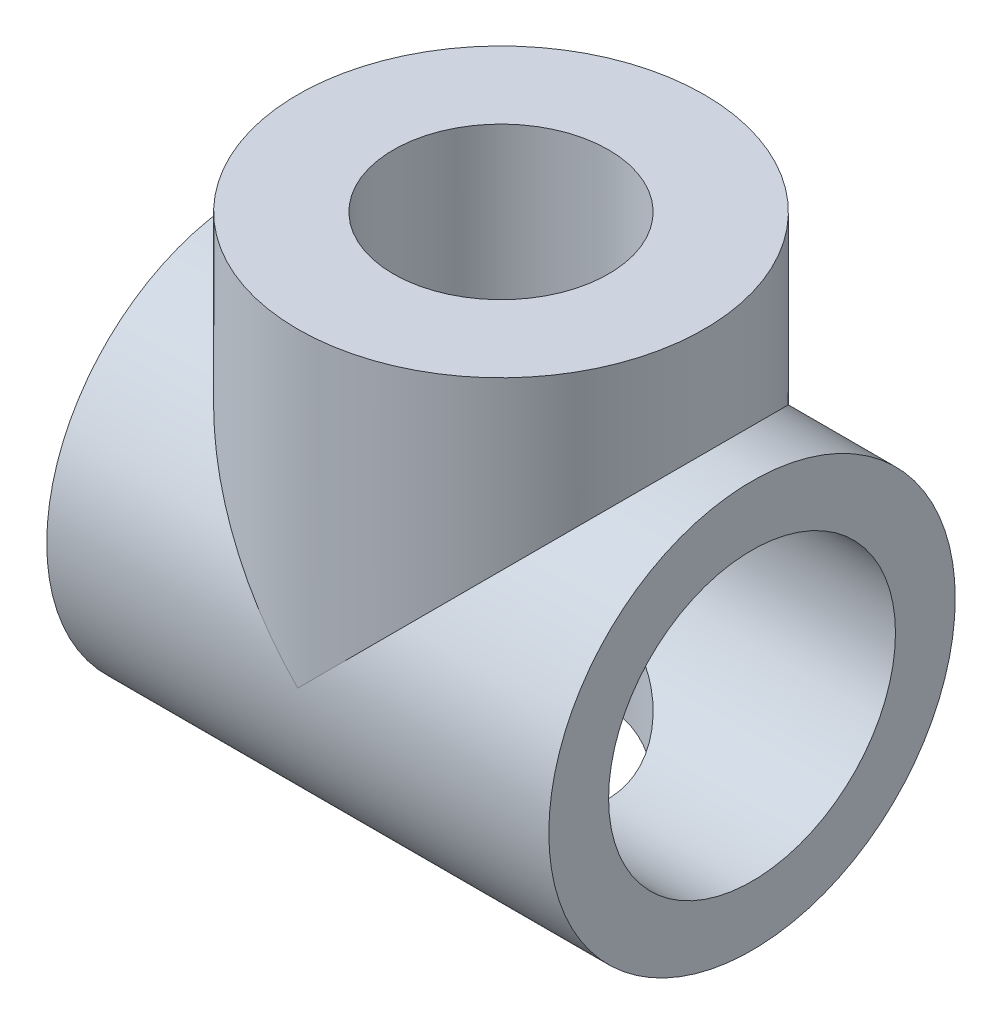
SolidWorks part; units mm, degrees
ref_plane "前视基准面" through (0, 0, 0) normal (0, 0, 1) x (1, 0, 0)
ref_plane "上视基准面" through (0, 0, 0) normal (0, 1, 0) x (1, 0, 0)
ref_plane "右视基准面" through (0, 0, 0) normal (1, 0, 0) x (0, 0, -1)
sketch "草图1" plane through (0, 0, 0) normal (0, 1, 0) x (1, 0, 0)
  circle A0 centre (0, 0) radius 17
extrude "凸台-拉伸1" add sketch "草图1" along normal blind 26
sketch "草图2" plane through (0, 0, 0) normal (1, 0, 0) x (0, 0, -1)
  circle A0 centre (0, 0) radius 17
extrude "凸台-拉伸2" add sketch "草图2" along normal blind 21 and the other way blind 21
sketch "草图4" plane through (0, 0, 0) normal (1, 0, 0) x (0, 0, -1)
  circle A0 centre (0, 0) radius 12
extrude "切除-拉伸2" cut sketch "草图4" against normal blind 21 and the other way blind 21
sketch "草图5" plane through (0, 0, 0) normal (0, 1, 0) x (1, 0, 0)
  circle A0 centre (0, 0) radius 9
  point P3 (0, 0)
extrude "切除-拉伸3" cut sketch "草图5" against normal blind 17 and the other way blind 26
